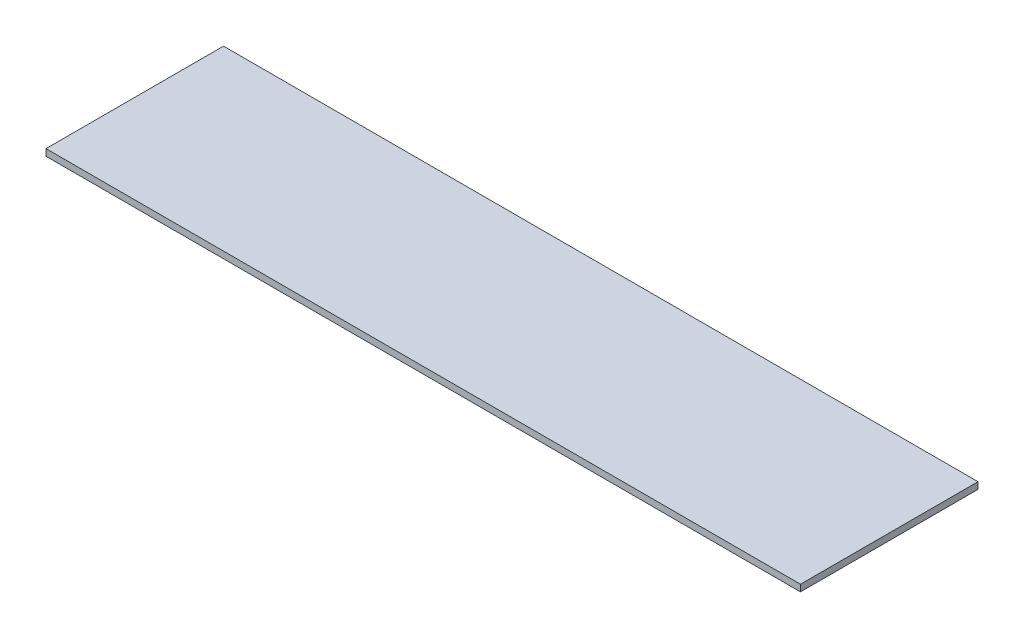
SolidWorks part; units mm, degrees
ref_plane "Front Plane" through (0, 0, 0) normal (0, 0, 1) x (1, 0, 0)
ref_plane "Top Plane" through (0, 0, 0) normal (0, 1, 0) x (1, 0, 0)
ref_plane "Right Plane" through (0, 0, 0) normal (1, 0, 0) x (0, 0, -1)
sketch "Sketch1" plane through (0, 0, 0) normal (0, 1, 0) x (1, 0, 0)
  line L1 (-1900, 450) -> (1500, 450)
  line L2 (-1900, 450) -> (-1900, -350)
  line L3 (-1900, -350) -> (1500, -350)
  line L4 (1500, 450) -> (1500, -350)
  dimension "D1" = 3400
  dimension "D2" = 800
  dimension "D3" = 350
  dimension "D4" = 1500
extrude "Boss-Extrude1" add sketch "Sketch1" along normal blind 30
